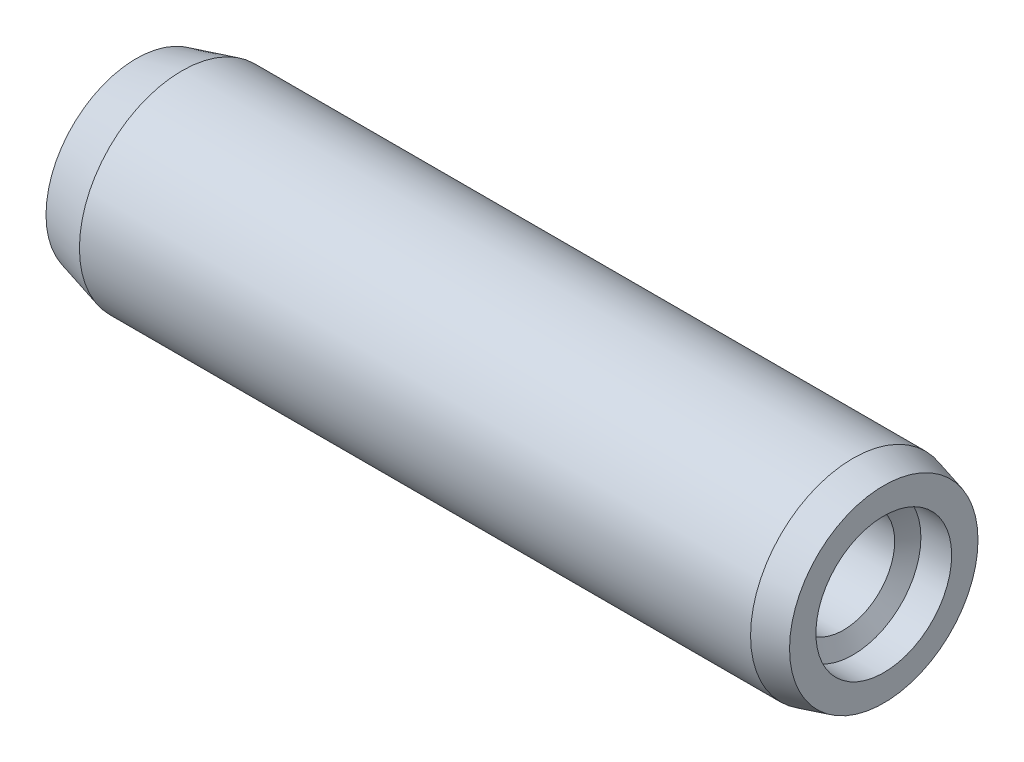
SolidWorks part; units mm, degrees
ref_plane "Plan1" through (0, 0, 0) normal (0, 0, 1) x (1, 0, 0)
ref_plane "Plan2" through (0, 0, 0) normal (0, 1, 0) x (1, 0, 0)
ref_plane "Plan3" through (0, 0, 0) normal (1, 0, 0) x (0, 0, -1)
sketch "Esquisse1" plane through (0, 0, 0) normal (0, 0, 1) x (1, 0, 0)
  line L0 (-7.0625, 0) -> (36.9107, 0) construction
  line L1 (0.8171, 3.5223) -> (2.6, 4)
  line L2 (2.6, 4) -> (28.8, 4)
  line L3 (28.8, 4) -> (30, 3.6785)
  line L4 (30, 3.6785) -> (30, 0)
  line L5 (30, 0) -> (0, 0)
  arc A0 (0.8171, 3.5223) -> (0, 0) centre (8, 0) ccw
  dimension "D1" = 8
  dimension "D2" = 30
  dimension "D3" = 15
  dimension "D4" = 1.2
  dimension "D5" = 2.6
  dimension "D6" = 15
  dimension "D7" = 4
revolve "Base-Révolution" add sketch "Esquisse1" angle 360 about L0
hole_wizard "Perçage1" positions "Esquisse4" profile "Esquisse3"
sketch "Esquisse4" plane through (30, 0, 0) normal (1, 0, 0) x (0, 0, -1)
  point P0 (0, 0)
sketch "Esquisse3" plane through (30, 0, 0) normal (0, 1, 0) x (0, 0, -1)
  line L0 (0, 0) -> (0, 13.1547)
  line L1 (0, 13.1547) -> (2, 12)
  line L2 (2, 12) -> (2, 0)
  line L4 (2, 0) -> (0, 0)
  line L6 (0, 13.1547) -> (-2, 12) construction
  line L7 (0, -4.2442) -> (0, 117.3081) construction
  dimension "Diamètre" = 4
  dimension "Profondeur" = 12
  dimension "Angle" = 120
cosmetic thread "Représentation de filetage1"
hole_wizard "Perçage2" positions "Esquisse6" profile "Esquisse5" legacy
sketch "Esquisse6" plane through (30, 0, 0) normal (1, 0, 0) x (0, 0, -1)
  point P0 (0, 0)
sketch "Esquisse5" plane through (30, 0, 0) normal (0, 1, 0) x (0, 0, -1)
  line L0 (0, 0) -> (0, 2.73)
  line L1 (0, 2.73) -> (2.65, 1.2)
  line L2 (2.65, 1.2) -> (2.65, 0)
  line L4 (2.65, 0) -> (0, 0)
  line L6 (0, 2.73) -> (-2.65, 1.2) construction
  line L7 (0, -4.2442) -> (0, 117.3081) construction
  dimension "Diamètre" = 5.3
  dimension "Profondeur" = 1.2
  dimension "Angle" = 120
